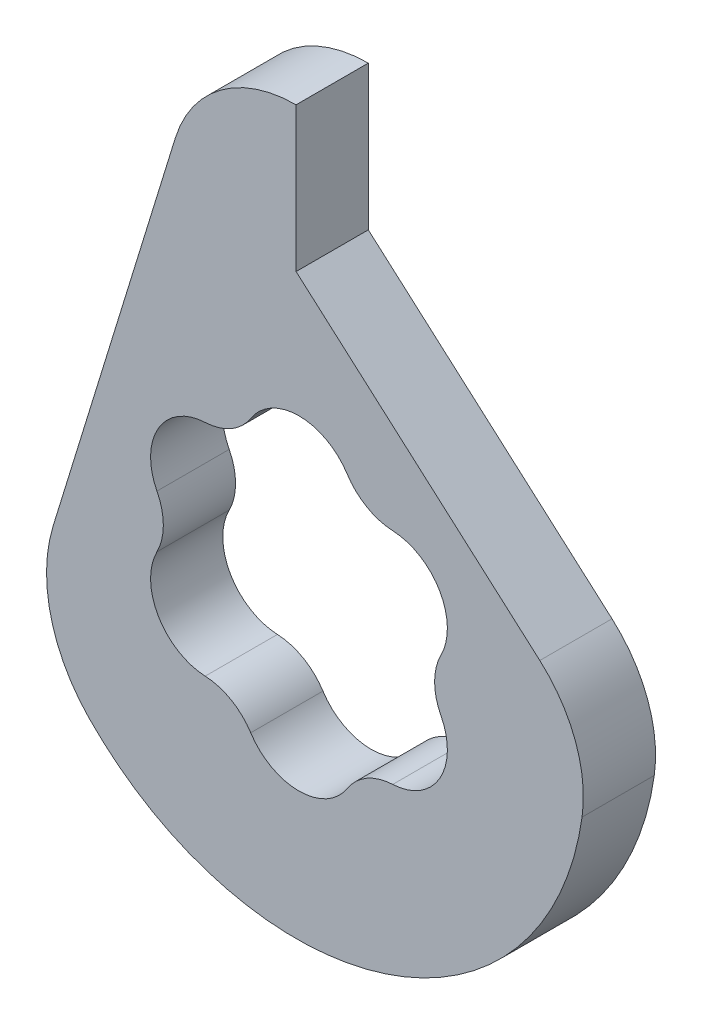
SolidWorks part; units mm, degrees
material "Alloy Steel"
ref_plane "Front Plane" through (0, 0, 0) normal (0, 0, 1) x (1, 0, 0)
ref_plane "Top Plane" through (0, 0, 0) normal (0, 1, 0) x (1, 0, 0)
ref_plane "Right Plane" through (0, 0, 0) normal (1, 0, 0) x (0, 0, -1)
other "Center of Mass"
sketch "Sketch1" plane through (0, 0, 0) normal (0, 0, 1) x (1, 0, 0)
  line L4 (0, 25.4) -> (0, 38.1)
  line L5 (-10.621, 30.2559) -> (-21.36, -4.6416)
  line L6 (0, 25.4) -> (21.4312, 6.4994)
  circle A10 centre (0, 0) radius 38.1 construction
  circle A11 centre (0, 0) radius 25.4 construction
  arc A12 (-18.215, -17.7024) -> (25.1475, -3.5726) centre (0, 0) ccw
  arc A13 (0, 38.1) -> (-10.621, 30.2559) centre (0, 26.9875) ccw
  circle A14 centre (0, 0) radius 15.875 construction
  arc A15 (-21.36, -4.6416) -> (-18.215, -17.7024) centre (-8.7643, -8.5177) ccw
  arc A16 (25.1475, -3.5726) -> (21.4312, 6.4994) centre (13.9513, -1.982) ccw
  circle A17 centre (0, 0) radius 19.05 construction
  point P2 (0, 0)
  point P15 (18.2966, 6.6259)
  point P17 (20.8934, 4.6684)
  dimension "D1" = 76.2
  dimension "D2" = 12.7
  dimension "D3" = 31.75
  dimension "D4" = 11.1125
  dimension "D5" = 36.5125
  dimension "D7" = 3.175
  dimension "D6" = 28.575
extrude "Boss-Extrude1" add sketch "Sketch1" along normal mid plane 6.35
sketch "Sketch2" plane through (0, 0, 3.175) normal (0, 0, 1) x (1, 0, 0)
  circle A0 centre (0.254, 0.254) radius 3.175
  point P2 (0, 0)
  point P3 (0, 0)
  point P4 (0, 0)
  point P5 (2.0237, 1.3186)
  point P6 (0.1434, 0.364)
  point P7 (1.8421, 0.6748)
  point P8 (0, 0)
  dimension "D3" = 6.35
  dimension "D1" = 0.254
  dimension "D2" = 0.254
extrude "Cut-Extrude1" cut sketch "Sketch2" against normal through all
ref_axis "Axis1" through (0.254, 0.254, -3.175) along (0, 0, 1)
sketch "Sketch3" plane through (0, 0, 3.175) normal (0, 0, 1) x (1, 0, 0)
  arc A12 (-7.9916, 9.9132) -> (-3.9883, 12.2245) centre (-8.2306, 14.9497) ccw
  arc A13 (-7.9916, 9.9132) -> (-12.2339, 2.5653) centre (-7.7527, 4.8767) ccw
  arc A14 (-12.2339, -2.0573) -> (-12.2339, 2.5653) centre (-16.7151, 0.254) ccw
  arc A15 (-12.2339, -2.0573) -> (-7.9916, -9.4052) centre (-7.7527, -4.3687) ccw
  arc A16 (-3.9883, -11.7165) -> (-7.9916, -9.4052) centre (-8.2306, -14.4417) ccw
  arc A17 (-3.9883, -11.7165) -> (4.4963, -11.7165) centre (0.254, -8.9913) ccw
  arc A18 (8.4996, -9.4052) -> (4.4963, -11.7165) centre (8.7386, -14.4417) ccw
  arc A19 (8.4996, -9.4052) -> (12.7419, -2.0573) centre (8.2607, -4.3687) ccw
  arc A20 (12.7419, 2.5653) -> (12.7419, -2.0573) centre (17.2231, 0.254) ccw
  arc A21 (12.7419, 2.5653) -> (8.4996, 9.9132) centre (8.2607, 4.8767) ccw
  arc A22 (4.4963, 12.2245) -> (8.4996, 9.9132) centre (8.7386, 14.9497) ccw
  arc A23 (4.4963, 12.2245) -> (-3.9883, 12.2245) centre (0.254, 9.4993) ccw
  arc A24 (-7.9916, 9.9132) -> (-3.9883, 12.2245) centre (-8.2306, 14.9497) ccw
  arc A25 (-7.9916, 9.9132) -> (-12.2339, 2.5653) centre (-7.7527, 4.8767) ccw
  arc A26 (-12.2339, -2.0573) -> (-12.2339, 2.5653) centre (-16.7151, 0.254) ccw
  arc A27 (-12.2339, -2.0573) -> (-7.9916, -9.4052) centre (-7.7527, -4.3687) ccw
  arc A28 (-3.9883, -11.7165) -> (-7.9916, -9.4052) centre (-8.2306, -14.4417) ccw
  arc A29 (-3.9883, -11.7165) -> (4.4963, -11.7165) centre (0.254, -8.9913) ccw
  arc A30 (8.4996, -9.4052) -> (4.4963, -11.7165) centre (8.7386, -14.4417) ccw
  arc A31 (8.4996, -9.4052) -> (12.7419, -2.0573) centre (8.2607, -4.3687) ccw
  arc A32 (12.7419, 2.5653) -> (12.7419, -2.0573) centre (17.2231, 0.254) ccw
  arc A33 (12.7419, 2.5653) -> (8.4996, 9.9132) centre (8.2607, 4.8767) ccw
  arc A34 (4.4963, 12.2245) -> (8.4996, 9.9132) centre (8.7386, 14.9497) ccw
  arc A35 (4.4963, 12.2245) -> (-3.9883, 12.2245) centre (0.254, 9.4993) ccw
  dimension "D1" = 0
extrude "Cut-Extrude2" cut sketch "Sketch3" against normal through all
